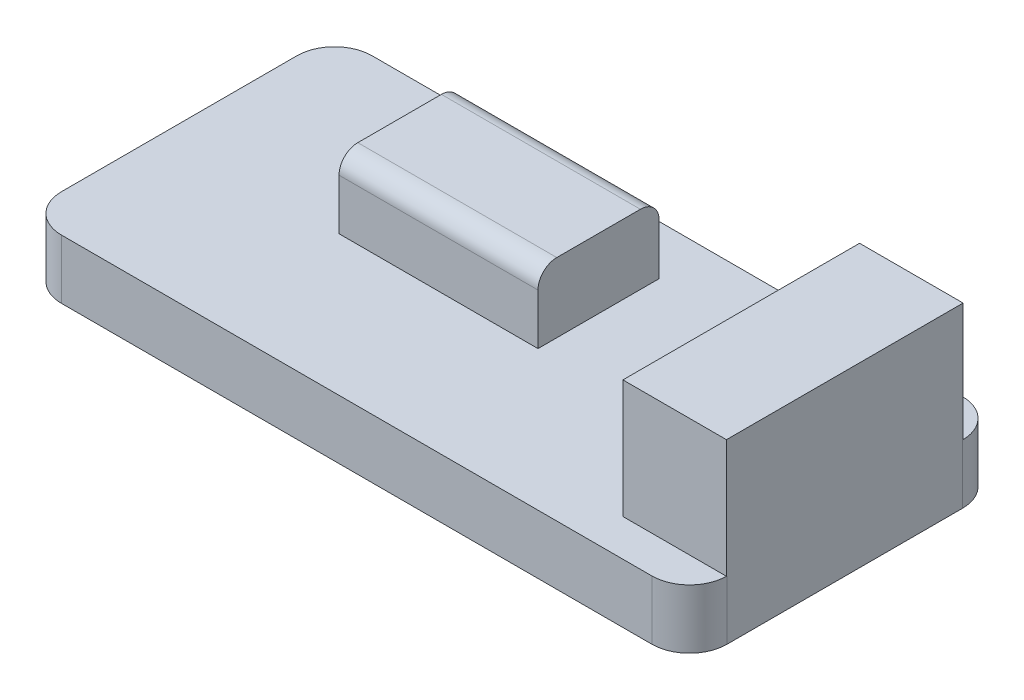
SolidWorks part; units mm, degrees
ref_plane "Front Plane" through (0, 0, 0) normal (0, 0, 1) x (1, 0, 0)
ref_plane "Top Plane" through (0, 0, 0) normal (0, 1, 0) x (1, 0, 0)
ref_plane "Right Plane" through (0, 0, 0) normal (1, 0, 0) x (0, 0, -1)
sketch "Sketch1" plane through (0, 0, 0) normal (0, 1, 0) x (1, 0, 0)
  line L1 (-19.96, -10.5) -> (19.96, -10.5)
  line L2 (-22.5, -7.96) -> (-22.5, 7.96)
  line L3 (-19.96, 10.5) -> (19.96, 10.5)
  line L4 (22.5, -7.96) -> (22.5, 7.96)
  line L5 (-22.5, -10.5) -> (22.5, 10.5) construction
  line L6 (-22.5, 10.5) -> (22.5, -10.5) construction
  arc A0 (19.96, 10.5) -> (22.5, 7.96) centre (19.96, 7.96) cw
  arc A1 (19.96, -10.5) -> (22.5, -7.96) centre (19.96, -7.96) ccw
  arc A2 (-19.96, -10.5) -> (-22.5, -7.96) centre (-19.96, -7.96) cw
  arc A3 (-22.5, 7.96) -> (-19.96, 10.5) centre (-19.96, 7.96) cw
  point P0 (0, 0)
  dimension "D3" = 2.54
  dimension "D1" = 45
  dimension "D2" = 21
extrude "Boss-Extrude1" add sketch "Sketch1" along normal blind 4
sketch "Sketch2" plane through (0, 4, 0) normal (0, 1, 0) x (1, 0, 0)
  line L0 (-22.5, 0) -> (22.5, 0) construction
  line L1 (22.5, -7.96) -> (22.5, 7.96) construction
  line L3 (15.5, -8) -> (22.5, -8)
  line L4 (15.5, -8) -> (15.5, 8)
  line L5 (15.5, 8) -> (22.5, 8)
  line L6 (22.5, -8) -> (22.5, 8)
  line L7 (15.5, -8) -> (22.5, 8) construction
  line L8 (15.5, 8) -> (22.5, -8) construction
  point P0 (19, 0)
  point P6 (0, 0)
  dimension "D1" = 16
  dimension "D2" = 7
  dimension "D3" = 0
extrude "Boss-Extrude2" add sketch "Sketch2" along normal blind 8
sketch "Sketch3" plane through (0, 4, 0) normal (0, 1, 0) x (1, 0, 0)
  line L1 (-10.6548, 7.1542) -> (2.7975, 7.1542)
  line L2 (-10.6548, 7.1542) -> (-10.6548, -1.0395)
  line L3 (-10.6548, -1.0395) -> (2.7975, -1.0395)
  line L4 (2.7975, 7.1542) -> (2.7975, -1.0395)
extrude "Boss-Extrude3" add sketch "Sketch3" along normal blind 4.698
fillet "Fillet1" radius 1.27 2 edges at (-3.9287, 8.698, -7.1542) (-3.9287, 8.698, 1.0395)
